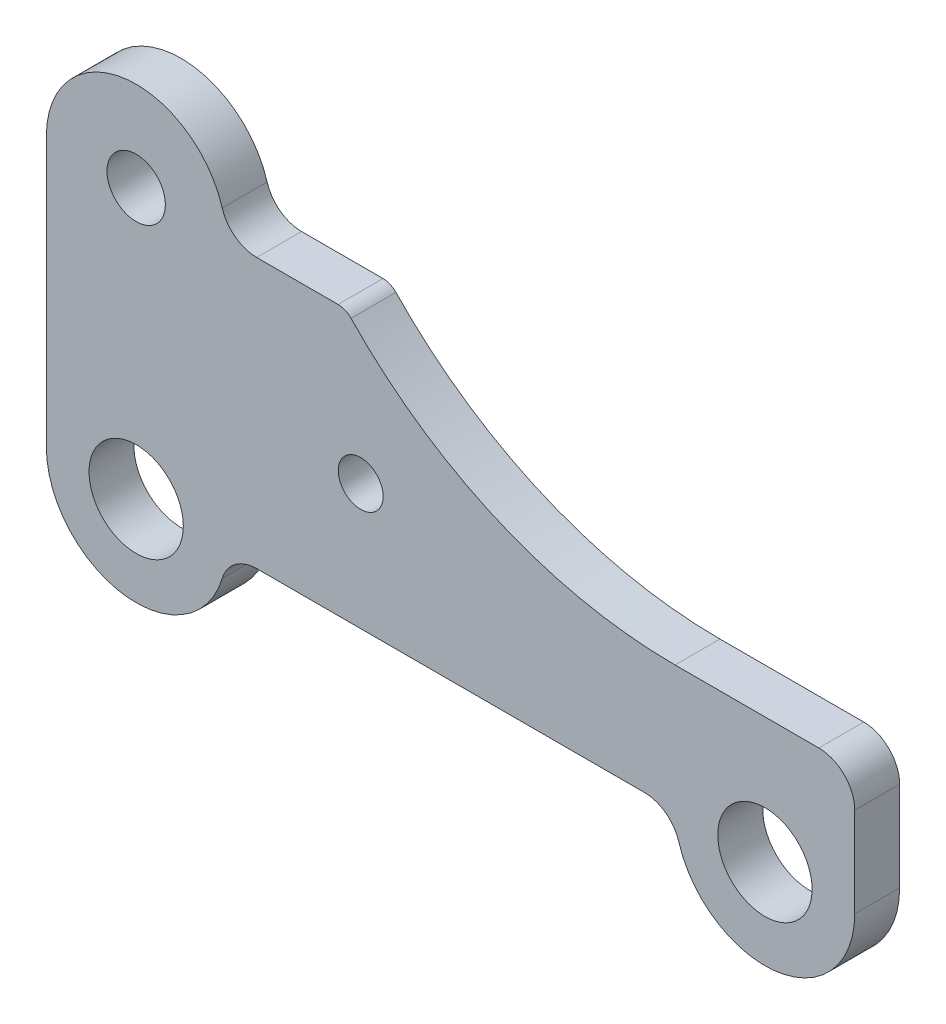
SolidWorks part; units mm, degrees
ref_plane "Płaszczyzna przednia" through (0, 0, 0) normal (0, 0, 1) x (1, 0, 0)
ref_plane "Płaszczyzna górna" through (0, 0, 0) normal (0, 1, 0) x (1, 0, 0)
ref_plane "Płaszczyzna prawa" through (0, 0, 0) normal (1, 0, 0) x (0, 0, -1)
sketch "Szkic1" plane through (0, 0, 0) normal (0, 0, 1) x (1, 0, 0)
  line L0 (0, 40) -> (0, 0) construction
  line L1 (0, 0) -> (73.2903, 0) construction
  line L2 (10, 40) -> (10, 10) construction
  line L3 (10, 10) -> (60.7436, 10) construction
  line L4 (0, 40) -> (0, 10)
  line L5 (23.4164, 10) -> (66.5836, 10)
  line L6 (90, 10) -> (90, 20)
  line L7 (86, 24) -> (70, 24)
  line L8 (32.4767, 40) -> (23.4164, 40)
  arc A0 (0, 10) -> (19.5831, 7.1429) centre (10, 10) ccw
  arc A1 (70.4169, 7.1429) -> (90, 10) centre (80, 10) ccw
  arc A2 (70, 24) -> (33.9199, 39.3846) centre (70, 74) cw
  arc A3 (19.5831, 42.8571) -> (0, 40) centre (10, 40) ccw
  circle A4 centre (10, 40) radius 3.25
  circle A5 centre (10, 10) radius 5.25
  circle A6 centre (80, 10) radius 5.25
  circle A8 centre (35, 24) radius 2.5
  arc A9 (90, 20) -> (86, 24) centre (86, 20) ccw
  arc A10 (66.5836, 10) -> (70.4169, 7.1429) centre (66.5836, 6) cw
  arc A11 (19.5831, 7.1429) -> (23.4164, 10) centre (23.4164, 6) cw
  arc A12 (23.4164, 40) -> (19.5831, 42.8571) centre (23.4164, 44) cw
  arc A13 (33.9199, 39.3846) -> (32.4767, 40) centre (32.4767, 38) ccw
  point P24 (90, 24)
  point P27 (70, 10)
  point P30 (20, 10)
  point P33 (20, 40)
  dimension "D6" = 50
  dimension "D8" = 10
  dimension "D9" = 10.5
  dimension "D10" = 5
  dimension "D13" = 6.5
  dimension "D14" = 4
  dimension "D15" = 2
  dimension "D1" = 40
  dimension "D2" = 10
  dimension "D3" = 10
  dimension "D4" = 70
  dimension "D5" = 14
  dimension "D7" = 20
  dimension "D11" = 24
  dimension "D12" = 25
extrude "Dodanie-wyciągnięcie1" add sketch "Szkic1" along normal mid plane 5
sketch "Szkic2" plane through (0, 0, -2.5) normal (0, 0, -1) x (-1, 0, 0)
  text T0 "Cannon model\r\nby Jaro" font "Bernard MT Condensed" height 2
extrude "Dodanie-wyciągnięcie2" add sketch "Szkic2" along normal blind 0.5
